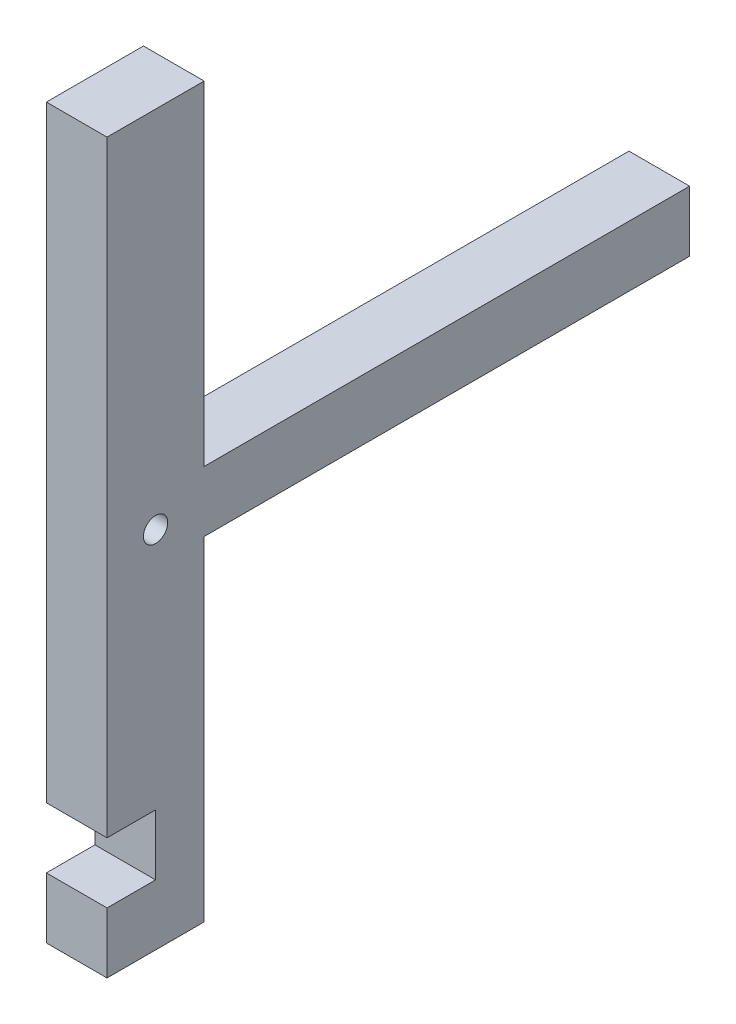
SolidWorks part; units mm, degrees
ref_plane "Front Plane" through (0, 0, 0) normal (0, 0, 1) x (1, 0, 0)
ref_plane "Top Plane" through (0, 0, 0) normal (0, 1, 0) x (1, 0, 0)
ref_plane "Right Plane" through (0, 0, 0) normal (1, 0, 0) x (0, 0, -1)
sketch "Elevator Paddle" plane through (0, 0, 0) normal (1, 0, 0) x (0, 0, -1)
  line L0 (-5.08, 0) -> (55.4696, 0) construction
  line L1 (-5.08, -38.1) -> (5.08, -38.1)
  line L2 (-5.08, -38.1) -> (-5.08, -31.75)
  line L3 (-5.08, 38.1) -> (5.08, 38.1)
  line L4 (5.08, -38.1) -> (5.08, -3.175)
  line L5 (-5.08, -38.1) -> (5.08, 38.1) construction
  line L6 (-5.08, 38.1) -> (5.08, -38.1) construction
  line L7 (5.08, -3.175) -> (55.88, -3.175)
  line L9 (5.08, 3.175) -> (55.88, 3.175)
  line L10 (55.88, -3.175) -> (55.88, 3.175)
  line L11 (0, 38.1) -> (0, -38.1) construction
  line L12 (-5.08, -31.75) -> (0, -31.75)
  line L13 (5.08, 3.175) -> (5.08, 38.1)
  line L14 (-5.08, -25.4) -> (0, -25.4)
  line L15 (0, -31.75) -> (0, -25.4)
  line L16 (-5.08, -25.4) -> (-5.08, 38.1)
  circle A0 centre (0, 0) radius 1.27
  point P0 (0, 0)
  point P14 (55.88, 0)
  dimension "D3" = 2.54
  dimension "D1" = 76.2
  dimension "D2" = 10.16
  dimension "D4" = 6.35
  dimension "D5" = 50.8
  dimension "D6" = 6.35
  dimension "D7" = 6.35
extrude "Boss-Extrude1" add sketch "Elevator Paddle" along normal blind 6.35 contours L16 L14 L15 L12 L2 L1 L4 L7 L10 L9 L13 L3 A0 region at (0, 0.8701, -9.3579)
equation "\"Ball Diameter\"= 1.75in"
equation "\"Sheet Thickness\"= 0.25in"
equation "\"Screw Diameter\"= .17in"
equation "\"Robot Diameter\"= 14in"
equation "\"Castor Screw Diameter\"= 0.22in"
equation "\"Wheel Diameter\" = 4in"
equation "\"Nut Diameter\" = 8.4mm"
equation "\"Nut Height\" = 2.9mm"
equation "\"Screw Height\" = 0.55in"
equation "\"D4@Elevator Paddle\"=\"Sheet Thickness\""
equation "\"D5@Elevator Paddle\"=\"Ball Diameter\"+0.25in"
equation "\"D6@Elevator Paddle\"=\"Sheet Thickness\""
equation "\"D7@Elevator Paddle\"=\"Sheet Thickness\""
equation "\"D1@Boss-Extrude1\"=\"Sheet Thickness\""
